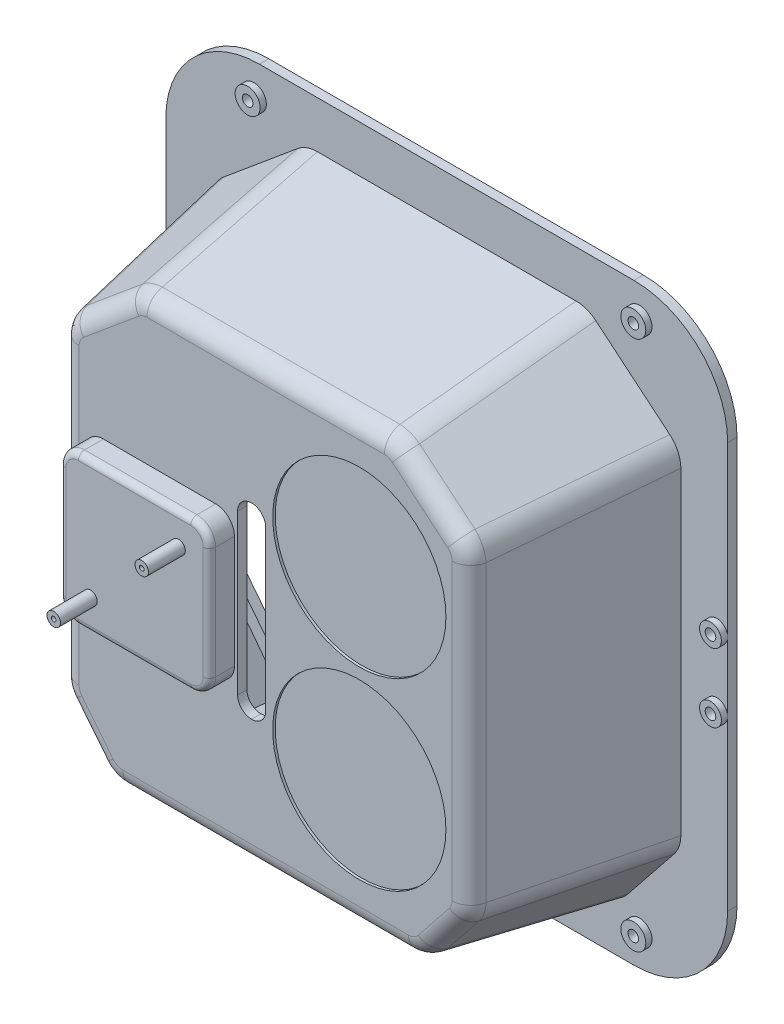
SolidWorks part; units mm, degrees
ref_plane "Front Plane" through (0, 0, 0) normal (0, 0, 1) x (1, 0, 0)
ref_plane "Top Plane" through (0, 0, 0) normal (0, 1, 0) x (1, 0, 0)
ref_plane "Right Plane" through (0, 0, 0) normal (1, 0, 0) x (0, 0, -1)
sketch "SK_Brim_180x190" plane through (0, 0, 0) normal (0, 0, 1) x (1, 0, 0)
  line L1 (-90, -95) -> (90, -95)
  line L2 (-90, -95) -> (-90, 95)
  line L3 (-90, 95) -> (90, 95)
  line L4 (90, -95) -> (90, 95)
  line L5 (-72, -77) -> (72, -77)
  line L6 (-72, -77) -> (-72, 77)
  line L7 (-72, 77) -> (72, 77)
  line L8 (72, -77) -> (72, 77)
extrude "Board_Mount_Brim_3mm" add sketch "SK_Brim_180x190" along normal blind 3
fillet "Brim_Outer_R30" radius 30 4 edges at (-90, 95, 1.5) (90, 95, 1.5) (90, -95, 1.5) (-90, -95, 1.5)
fillet "Brim_Inner_R10" radius 10 4 edges at (-72, 77, 1.5) (72, 77, 1.5) (72, -77, 1.5) (-72, -77, 1.5)
sketch "SK_Cockpit_Octagon" plane through (0, 0, 3) normal (0, 0, 1) x (1, 0, 0)
  line L0 (-55, -80) -> (55, -80)
  line L1 (55, -80) -> (75, -55)
  line L2 (75, -55) -> (75, 55)
  line L3 (75, 55) -> (45, 80)
  line L4 (45, 80) -> (-45, 80)
  line L5 (-45, 80) -> (-75, 55)
  line L6 (-75, 55) -> (-75, -55)
  line L7 (-75, -55) -> (-55, -80)
extrude "Cockpit_Canopy_Draft10deg" add sketch "SK_Cockpit_Octagon" along normal blind 58 draft 10
fillet "Canopy_Corners_R10" radius 10 8 edges at (-69.8865, -53.2063, 32) (-69.8865, 52.605, 32) (-43.1487, 74.8865, 32) (43.1487, 74.8865, 32) (69.8865, 52.605, 32) (69.8865, -53.2063, 32) (52.5423, -74.8865, 32) (-52.5423, -74.8865, 32)
fillet "Canopy_Roof_R6" radius 6 16 edges at (-57.8283, -60.0936, 61) (0, -69.773, 61) (57.8283, -60.0936, 61) (64.773, -1.1804, 61) (52.633, 60.3267, 61) (0, 69.773, 61) (-52.633, 60.3267, 61) (-64.773, -1.1804, 61) (-49.6183, -68.8027, 61) (49.6183, -68.8027, 61) (64.2184, -51.218, 61) (63.8447, 49.7752, 61) (41.0846, 69.1854, 61) (-41.0846, 69.1854, 61) (-63.8447, 49.7752, 61) (-64.2184, -51.218, 61)
sketch "SK_Symmetric_Cavity" plane through (0, 0, 0) normal (0, 0, -1) x (-1, 0, 0)
  line L0 (-53, -77) -> (53, -77)
  line L1 (57.3444, -77) -> (-57.3444, -77) construction
  line L2 (53, -77) -> (72, -52)
  line L3 (72, 57.4649) -> (72, -58.75) construction
  line L4 (72, -52) -> (72, 52)
  line L5 (72, 52) -> (43, 77)
  line L6 (-62, 77) -> (62, 77) construction
  line L7 (43, 77) -> (-43, 77)
  line L8 (-43, 77) -> (-72, 52)
  line L9 (-72, -67) -> (-72, 67) construction
  line L10 (-72, 52) -> (-72, -52)
  line L11 (-72, -52) -> (-53, -77)
extrude "Symmetric_Electronics_Cavity_58H" cut sketch "SK_Symmetric_Cavity" against normal blind 58 draft 10
sketch "Sketch14" plane through (0, 0, 61) normal (0, 0, 1) x (1, 0, 0)
  line L1 (-58, -24) -> (-10, -24)
  line L2 (-58, -24) -> (-58, 24)
  line L3 (-58, 24) -> (-10, 24)
  line L4 (-10, -24) -> (-10, 24)
extrude "Boss-Extrude5" add sketch "Sketch14" along normal blind 8
fillet "Fillet3" radius 6 4 edges at (-58, 24, 65) (-10, 24, 65) (-10, -24, 65) (-58, -24, 65)
fillet "Fillet4" radius 2 8 edges at (-58, 0, 69) (-34, -24, 69) (-10, 0, 69) (-34, 24, 69) (-56.2426, -22.2426, 69) (-11.7574, -22.2426, 69) (-11.7574, 22.2426, 69) (-56.2426, 22.2426, 69)
sketch "Sketch15" plane through (0, 0, 69) normal (0, 0, 1) x (1, 0, 0)
  circle A0 centre (-48.1, -14.1) radius 2.15
  circle A1 centre (-19.9, 14.1) radius 2.15
extrude "Boss-Extrude6" add sketch "Sketch15" along normal blind 11.8
sketch "Sketch16" plane through (0, 0, 80.8) normal (0, 0, 1) x (1, 0, 0)
  circle A0 centre (-48.1, -14.1) radius 0.75
  circle A1 centre (-19.9, 14.1) radius 0.75
extrude "Cut-Extrude10" cut sketch "Sketch16" against normal blind 11.3
sketch "Sketch19" plane through (0, 0, 0) normal (0, 0, 1) x (1, 0, 0)
  line L0 (-50, -73) -> (50, -73)
  line L1 (-72, -77) -> (72, -77)
  line L2 (-72, -77) -> (-72, 77)
  line L3 (-72, 77) -> (72, 77)
  line L4 (72, -77) -> (72, 77)
  line L5 (50, -73) -> (68, -50)
  line L6 (68, -50) -> (68, 50)
  line L7 (68, 50) -> (40, 73)
  line L8 (40, 73) -> (-40, 73)
  line L9 (-40, 73) -> (-68, 50)
  line L10 (-68, 50) -> (-68, -50)
  line L11 (-68, -50) -> (-50, -73)
extrude "Boss-Extrude7" add sketch "Sketch19" along normal blind 3
sketch "Sketch20" plane through (0, 0, 3) normal (0, 0, 1) x (1, 0, 0)
  circle A0 centre (-86.5, -11) radius 1.7
  circle A1 centre (-86.5, 11) radius 1.7
  circle A2 centre (86.5, -11) radius 1.7
  circle A3 centre (86.5, 11) radius 1.7
  circle A4 centre (-61.7761, -84.9997) radius 1.7
  circle A5 centre (61.7761, -84.9997) radius 1.7
  circle A6 centre (-61.7761, 84.9997) radius 1.7
  circle A7 centre (61.7761, 84.9997) radius 1.7
extrude "Cut-Extrude13" cut sketch "Sketch20" against normal blind 3.2
sketch "Sketch21" plane through (0, 0, 61) normal (0, 0, 1) x (1, 0, 0)
  circle A0 centre (30, -29.5) radius 27.75
extrude "Cut-Extrude14" cut sketch "Sketch21" against normal blind 0.8
sketch "Sketch22" plane through (0, 0, 61) normal (0, 0, 1) x (1, 0, 0)
  circle A0 centre (30, 29.5) radius 27.75
extrude "Cut-Extrude15" cut sketch "Sketch22" against normal blind 0.8
sketch "Sketch24" plane through (0, 0, 61) normal (0, 0, 1) x (1, 0, 0)
  line L1 (-9, -30) -> (0, -30)
  line L2 (-9, -30) -> (-9, 30)
  line L3 (-9, 30) -> (0, 30)
  line L4 (0, -30) -> (0, 30)
extrude "Cut-Extrude18" cut sketch "Sketch24" against normal blind 4
fillet "Fillet5" radius 4.5 4 edges at (-9, -30, 59.5) (0, -30, 59.5) (0, 30, 59.5) (-9, 30, 59.5)
sketch "Sketch25" plane through (0, 0, 3) normal (0, 0, 1) x (1, 0, 0)
  circle A0 centre (-86.5, -11) radius 4
  circle A1 centre (-86.5, -11) radius 1.7
  circle A2 centre (-86.5, 11) radius 4
  circle A3 centre (-86.5, 11) radius 1.7
  circle A4 centre (86.5, -11) radius 3.5
  circle A5 centre (86.5, -11) radius 1.7
  circle A6 centre (86.5, 11) radius 3.5
  circle A7 centre (86.5, 11) radius 1.7
  circle A8 centre (-61.7761, -84.9997) radius 4
  circle A9 centre (-61.7761, -84.9997) radius 1.7
  circle A10 centre (61.7761, -84.9997) radius 4
  circle A11 centre (61.7761, -84.9997) radius 1.7
  circle A12 centre (-61.7761, 84.9997) radius 4
  circle A13 centre (-61.7761, 84.9997) radius 1.7
  circle A14 centre (61.7761, 84.9997) radius 4
  circle A15 centre (61.7761, 84.9997) radius 1.7
extrude "Boss-Extrude8" add sketch "Sketch25" along normal blind 2
